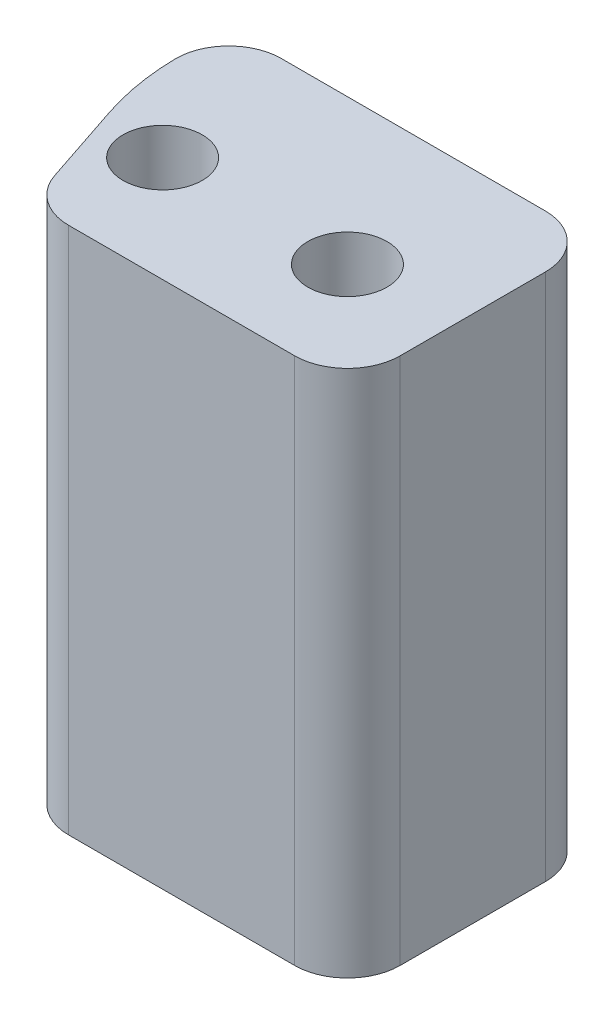
SolidWorks part; units mm, degrees
ref_plane "Front Plane" through (0, 0, 0) normal (0, 0, 1) x (1, 0, 0)
ref_plane "Top Plane" through (0, 0, 0) normal (0, 1, 0) x (1, 0, 0)
ref_plane "Right Plane" through (0, 0, 0) normal (1, 0, 0) x (0, 0, -1)
sketch "Sketch1" plane through (0, 0, 0) normal (0, 1, 0) x (1, 0, 0)
  line L0 (0, 6.0325) -> (0, -6.0325) construction
  line L1 (-8.89, 6.0325) -> (8.89, 6.0325)
  line L2 (-8.89, 6.0325) -> (-8.89, -6.0325)
  line L3 (-8.89, -6.0325) -> (8.89, -6.0325)
  line L4 (8.89, 6.0325) -> (8.89, -6.0325)
  line L5 (-8.89, 6.0325) -> (8.89, -6.0325) construction
  line L6 (-8.89, -6.0325) -> (8.89, 6.0325) construction
  circle A0 centre (-5.08, -0.9525) radius 1.905
  circle A1 centre (3.81, -0.9525) radius 1.905
  point P0 (0, 0)
  dimension "D2" = 3.81
  dimension "D1" = 17.78
  dimension "D3" = 12.065
  dimension "D4" = 5.08
  dimension "D5" = 8.89
  dimension "D6" = 3.81
extrude "Boss-Extrude1" add sketch "Sketch1" along normal blind 25.4
sketch "Sketch2" plane through (0, 25.4, 0) normal (0, 1, 0) x (1, 0, 0)
  line L0 (-8.89, 1.5875) -> (-6.35, -6.0325)
  line L1 (-8.89, 6.0325) -> (-8.89, -6.0325) construction
  line L2 (-8.89, 1.5875) -> (-8.89, -6.0325)
  line L3 (-8.89, -6.0325) -> (-6.35, -6.0325)
  dimension "D1" = 7.62
  dimension "D2" = 2.54
extrude "Cut-Extrude1" cut sketch "Sketch2" against normal through all
fillet "Fillet1" radius 2.54 4 edges at (-6.35, 12.7, 6.0325) (8.89, 12.7, -6.0325) (8.89, 12.7, 6.0325) (-8.89, 12.7, -6.0325)
fillet "Fillet2" radius 12.7 1 edges at (-8.89, 12.7, -1.5875)
